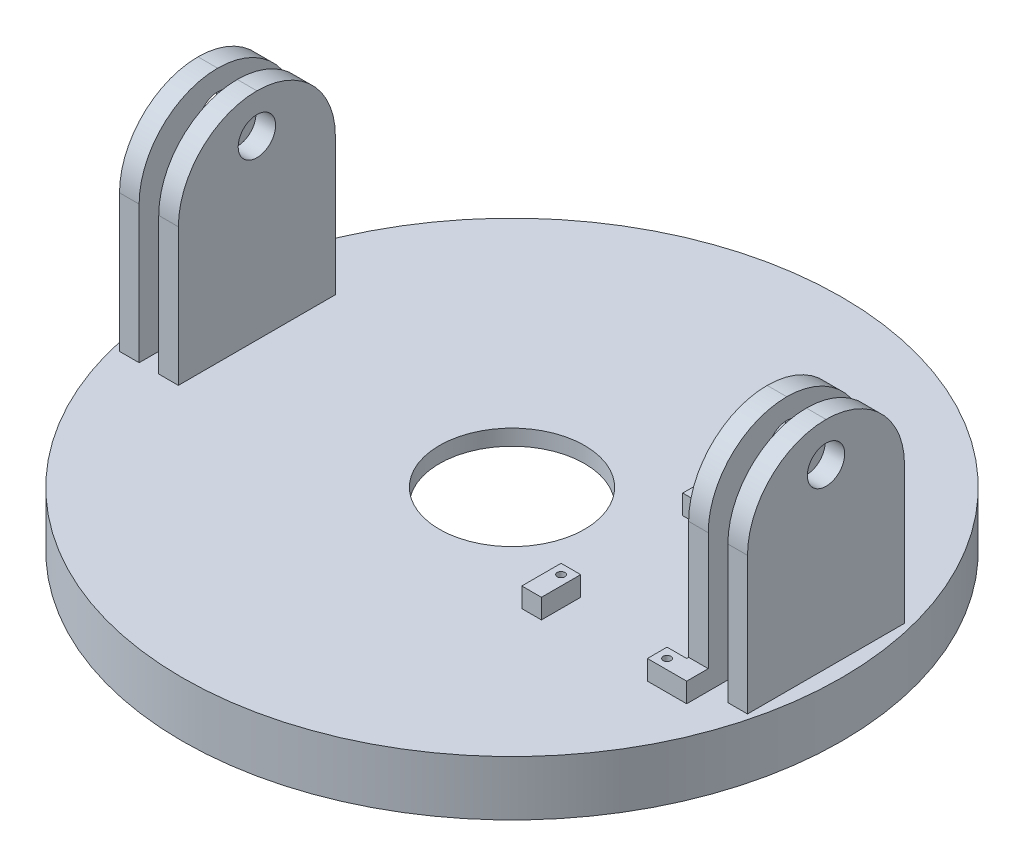
SolidWorks part; units mm, degrees
ref_plane "Alzado" through (0, 0, 0) normal (0, 0, 1) x (1, 0, 0)
ref_plane "Planta" through (0, 0, 0) normal (0, 1, 0) x (1, 0, 0)
ref_plane "Vista lateral" through (0, 0, 0) normal (1, 0, 0) x (0, 0, -1)
sketch "Croquis1" plane through (0, 0, 0) normal (0, 1, 0) x (1, 0, 0)
  circle A0 centre (0, 0) radius 84
  circle A1 centre (0, 0) radius 82
  dimension "D1" = 168
  dimension "D2" = 164
extrude "Saliente-Extruir1" add sketch "Croquis1" along normal blind 10
sketch "Croquis2" plane through (0, 10, 0) normal (0, 1, 0) x (1, 0, 0)
  circle A0 centre (0, 0) radius 84
  dimension "D1" = 168
extrude "Saliente-Extruir2" add sketch "Croquis2" along normal blind 4
sketch "Croquis3" plane through (0, 10, 0) normal (0, -1, 0) x (1, 0, 0)
  circle A0 centre (-20, 40) radius 1.5
  dimension "D1" = 3
  dimension "D6" = 40
  dimension "D7" = 20
extrude "Saliente-Extruir3" add sketch "Croquis3" along normal blind 10
ref_axis "Eje1" through (0, -0.7, 0) along (0, 1, 0)
pattern_circular "MatrizC1" count 4 every 90 about axis through (0, -0.7, 0) along (0, 1, 0) of "Saliente-Extruir3"
sketch "Croquis15" plane through (0, 0, 0) normal (0, -1, 0) x (1, 0, 0)
  circle A0 centre (0, 0) radius 82
  circle A1 centre (0, 0) radius 83
  dimension "D1" = 164
  dimension "D2" = 166
extrude "Cortar-Extruir1" cut sketch "Croquis15" against normal blind 5
sketch "Croquis16" plane through (0, 10, 0) normal (0, -1, 0) x (1, 0, 0)
  circle A0 centre (0, 0) radius 18.5
  dimension "D1" = 37
extrude "Cortar-Extruir2" cut sketch "Croquis16" against normal blind 13 contours A0
sketch "Croquis18" plane through (0, 14, 0) normal (0, 1, 0) x (1, 0, 0)
  line L0 (0, 0) -> (-84, 0) construction
  line L1 (0, 0) -> (0, 84) construction
  line L3 (-80, -20) -> (-65, -20)
  line L4 (-80, -20) -> (-80, 20)
  line L5 (-80, 20) -> (-65, 20)
  line L6 (-65, -20) -> (-65, 20)
  line L7 (-80, -20) -> (-65, 20) construction
  line L8 (-80, 20) -> (-65, -20) construction
  circle A0 centre (0, 0) radius 84 construction
  point P6 (-72.5, 0)
  dimension "D1" = 15
  dimension "D2" = 40
  dimension "D3" = 65
extrude "Saliente-Extruir4" add sketch "Croquis18" along normal blind 55
sketch "Croquis19" plane through (0, 69, 0) normal (0, 1, 0) x (1, 0, 0)
  line L0 (-65, 20) -> (-80, 20) construction
  line L1 (-75, 20) -> (-70, 20)
  line L2 (-75, 20) -> (-75, -20)
  line L3 (-75, -20) -> (-70, -20)
  line L4 (-70, 20) -> (-70, -20)
  line L5 (-80, -20) -> (-65, -20) construction
  line L6 (-80, 20) -> (-80, -20) construction
  dimension "D2" = 5
  dimension "D3" = 5
extrude "Cortar-Extruir3" cut sketch "Croquis19" against normal blind 55
sketch "Croquis20" plane through (-80, 0, 0) normal (-1, 0, 0) x (0, 0, 1)
  line L0 (-20, 69) -> (20, 69) construction
  line L1 (-20, 69) -> (-20, 14) construction
  circle A0 centre (0, 59) radius 4.7625
  dimension "D3" = 9.525
  dimension "D1" = 10
  dimension "D2" = 20
extrude "Cortar-Extruir4" cut sketch "Croquis20" against normal blind 40
fillet "Redondeo2" radius 20 4 edges at (-77.5, 69, 20) (-67.5, 69, 20) (-67.5, 69, -20) (-77.5, 69, -20)
mirror "Simetría1" about plane through (0, 0, 0) normal (1, 0, 0) of "Saliente-Extruir4", "Redondeo2", "Cortar-Extruir4", "Cortar-Extruir3"
sketch "Croquis21" plane through (65, 0, 0) normal (-1, 0, 0) x (0, 0, 1)
  line L0 (-20, 49) -> (-20, 14) construction
  line L2 (20, 14) -> (-20, 14) construction
  circle A0 centre (0, 34.5) radius 5
  dimension "D2" = 20.5
  dimension "D3" = 10
  dimension "D1" = 20
extrude "Cortar-Extruir5" cut sketch "Croquis21" against normal blind 10
sketch "Croquis22" plane through (0, 14, 0) normal (0, 1, 0) x (1, 0, 0)
  line L0 (0, 0) -> (-84, 0) construction
  line L1 (0, 0) -> (0, 84) construction
  line L2 (65, -20) -> (65, 20) construction
  line L7 (28, -15.5) -> (33, -15.5)
  line L9 (70, -25.5) -> (70, -20)
  line L11 (28, -25.5) -> (28, -15.5)
  line L12 (65, -20) -> (65, -20.5)
  line L14 (33, -15.5) -> (33, -25.5)
  line L16 (33, 25.5) -> (28, 25.5)
  line L20 (28, 15.5) -> (28, 25.5)
  line L21 (33, -25.5) -> (28, -25.5)
  line L22 (33, 25.5) -> (33, 15.5)
  line L23 (28, 15.5) -> (33, 15.5)
  line L25 (70, 20) -> (70, 25.5)
  line L27 (70, -20) -> (65, -20)
  line L28 (60, -20.5) -> (60, -25.5)
  line L29 (70, -25.5) -> (60, -25.5)
  line L30 (70, 20) -> (65, 20)
  line L31 (60, 20.5) -> (60, 25.5)
  line L32 (60, 25.5) -> (70, 25.5)
  line L34 (65, 20) -> (65, 20.5)
  line L35 (65, 20.5) -> (60, 20.5)
  line L36 (65, -20.5) -> (60, -20.5)
  circle A0 centre (0, 0) radius 84 construction
  point P5 (30.5, -25.5)
  dimension "D2" = 42
  dimension "D3" = 42
  dimension "D4" = 10
  dimension "D5" = 51
  dimension "D6" = 5.5
  dimension "D7" = 5.5
  dimension "D8" = 32
  dimension "D9" = 10
  dimension "D10" = 5
  dimension "D11" = 5
  dimension "D12" = 5
  dimension "D13" = 5
  dimension "D14" = 0.5
  dimension "D15" = 5
  dimension "D16" = 0.5
  dimension "D17" = 5
  dimension "D18" = 41
  dimension "D19" = 31
extrude "Saliente-Extruir6" add sketch "Croquis22" along normal blind 5
sketch "Croquis24" plane through (0, 14, 0) normal (0, 1, 0) x (1, 0, 0)
  line L0 (33, -25.5) -> (33, -15.5) construction
  line L2 (33, 25.5) -> (28, 25.5) construction
  line L3 (28, 25.5) -> (28, 15.5) construction
  line L4 (70, 25.5) -> (60, 25.5) construction
  line L5 (60, 25.5) -> (60, 20.5) construction
  line L6 (65, -20.5) -> (60, -20.5) construction
  line L7 (60, -20.5) -> (60, -25.5) construction
  line L8 (33, -15.5) -> (28, -15.5) construction
  circle A0 centre (30.5, 23) radius 0.9769
  circle A1 centre (62.5, 23) radius 0.9769
  circle A2 centre (30.5, -18) radius 0.9769
  circle A3 centre (62.5, -23) radius 0.9769
  dimension "D1" = 1.9538
  dimension "D2" = 1.9538
  dimension "D3" = 1.9538
  dimension "D4" = 1.9538
  dimension "D5" = 2.5
  dimension "D6" = 2.5
  dimension "D7" = 2.5
  dimension "D8" = 2.5
  dimension "D9" = 2.5
  dimension "D10" = 2.5
  dimension "D11" = 2.5
  dimension "D12" = 2.5
extrude "Cortar-Extruir6" cut sketch "Croquis24" along normal blind 6
